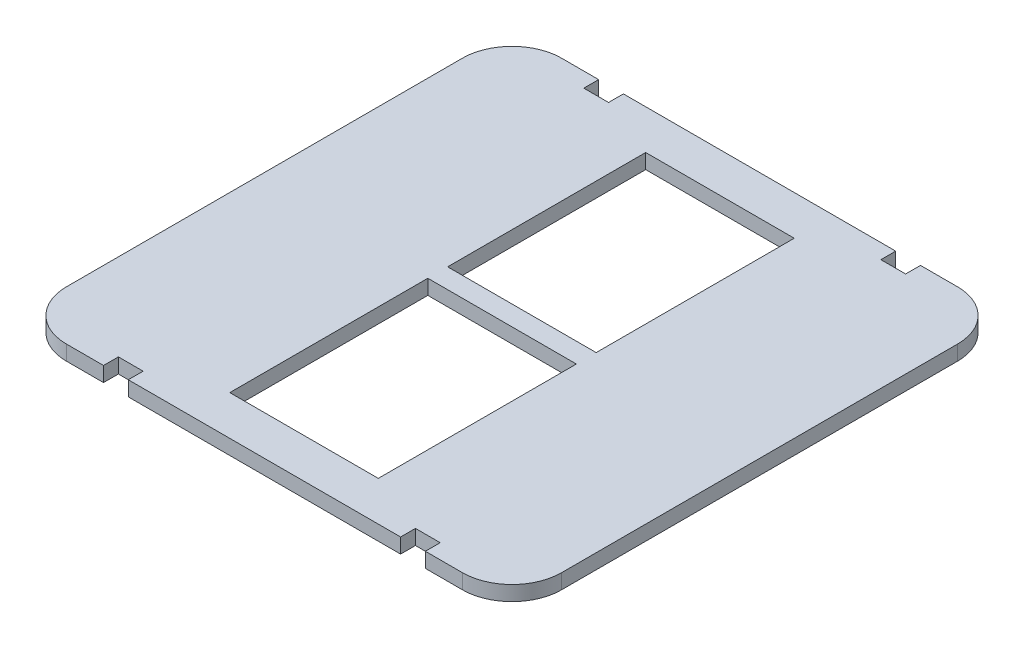
SolidWorks part; units mm, degrees
ref_plane "Front Plane" through (0, 0, 0) normal (0, 0, 1) x (1, 0, 0)
ref_plane "Top Plane" through (0, 0, 0) normal (0, 1, 0) x (1, 0, 0)
ref_plane "Right Plane" through (0, 0, 0) normal (1, 0, 0) x (0, 0, -1)
sketch "Sketch1" plane through (0, 0, 0) normal (0, 1, 0) x (1, 0, 0)
  line L1 (-127, -127) -> (127, -127)
  line L2 (-127, -127) -> (-127, 127)
  line L3 (-127, 127) -> (127, 127)
  line L4 (127, -127) -> (127, 127)
  line L5 (-127, -127) -> (127, 127) construction
  line L6 (-127, 127) -> (127, -127) construction
  point P0 (0, 0)
  dimension "D1" = 254
  dimension "D2" = 254
extrude "Platform-Base" add sketch "Sketch1" along normal blind 7.62
sketch "Sketch7" plane through (0, 7.62, 0) normal (0, 1, 0) x (1, 0, 0)
  line L0 (-127.3937, 0) -> (127, 0) construction
  line L2 (127, -127) -> (127, 127) construction
  line L3 (-38.1, -5.08) -> (38.1, -5.08)
  line L4 (-38.1, -5.08) -> (-38.1, -106.68)
  line L5 (-38.1, -106.68) -> (38.1, -106.68)
  line L6 (38.1, -5.08) -> (38.1, -106.68)
  line L7 (-38.1, -5.08) -> (38.1, -106.68) construction
  line L8 (-38.1, -106.68) -> (38.1, -5.08) construction
  line L9 (-0.1968, 0) -> (0, -55.88) construction
  dimension "D1" = 101.6
  dimension "D2" = 76.2
  dimension "D3" = 55.88
extrude "Cut-Extrude4" cut sketch "Sketch7" against normal through all
ref_axis "Axis1" through (-127, 7.62, 0) along (0, -1, 0)
ref_plane "Plane1" through (0, 0, 0) normal (0, 0, 1) x (0, -1, 0)
fillet "Corner-Rounding" radius 25.4 4 edges at (-127, 3.81, -127) (127, 3.81, -127) (127, 3.81, 127) (-127, 3.81, 127)
sketch "Sketch6" plane through (0, 7.62, 0) normal (0, 1, 0) x (1, 0, 0)
  line L0 (0, 0) -> (0, -127) construction
  line L1 (-101.6, -127) -> (101.6, -127) construction
  line L2 (0, -127) -> (-76.2, -127) construction
  line L3 (-76.2, -127) -> (-76.2, -123.19) construction
  line L5 (-82.55, -119.38) -> (-69.85, -119.38)
  line L6 (-82.55, -119.38) -> (-82.55, -127)
  line L7 (-82.55, -127) -> (-69.85, -127)
  line L8 (-69.85, -119.38) -> (-69.85, -127)
  line L9 (-82.55, -119.38) -> (-69.85, -127) construction
  line L10 (-82.55, -127) -> (-69.85, -119.38) construction
  dimension "D1" = 76.2
  dimension "D2" = 7.62
  dimension "D3" = 12.7
extrude "Cut-Extrude3" cut sketch "Sketch6" against normal through all
mirror "Mirror4" about plane through (0, 0, 0) normal (0, 0, 1) of "Cut-Extrude3"
mirror "Mirror5" about plane through (0, 0, 0) normal (0, 0, 1) of "Cut-Extrude4"
ref_axis "Axis2" through (0, 7.62, 5.08) along (0, 0, 1)
ref_plane "Plane2" through (0, 0, 0) normal (-1, 0, 0) x (0, 0, 1)
mirror "Mirror6" about plane through (0, 0, 0) normal (-1, 0, 0) of "Mirror4"
equation "\"Foamcore\" = .1in"
equation "\"MDF\" = .3in"
equation "\"Gmaterial\"= \"MDF\""
equation "\"D1@Platform-Base\" = \"Gmaterial\""
equation "\"D2@Sketch6\"=\"Gmaterial\""
